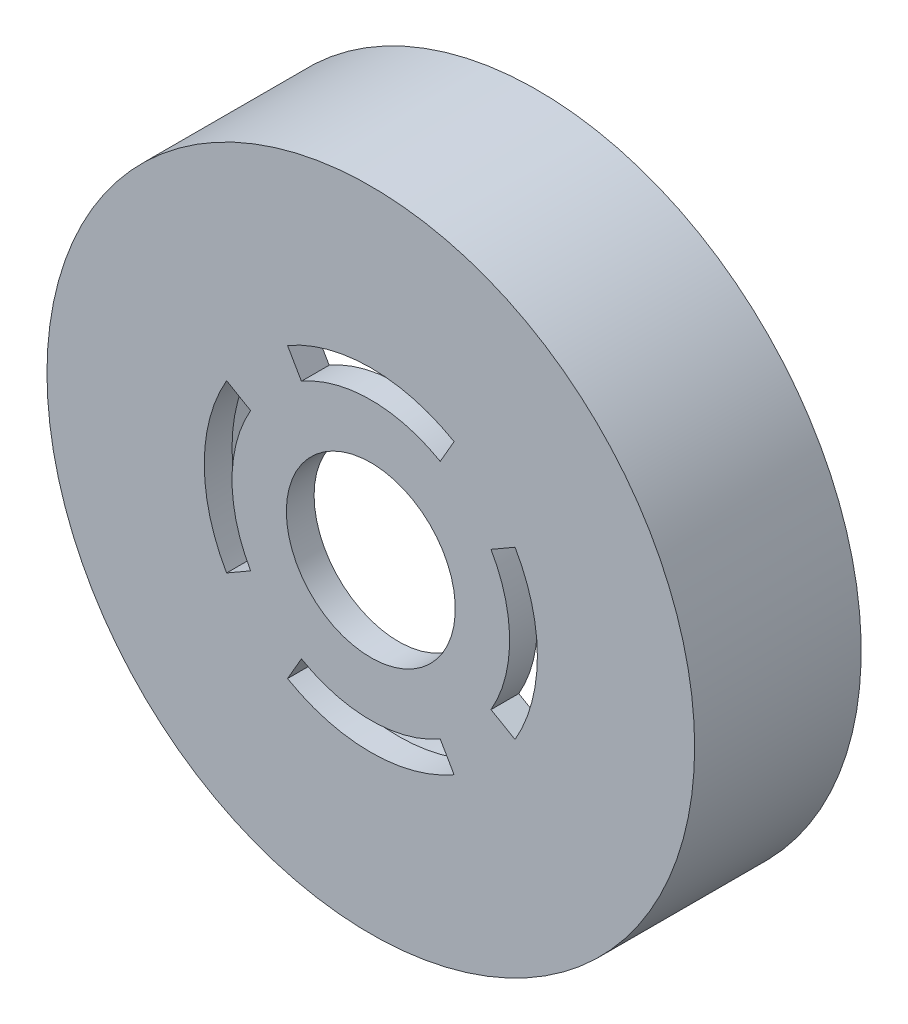
SolidWorks part; units mm, degrees
ref_plane "前视基准面" through (0, 0, 0) normal (0, 0, 1) x (1, 0, 0)
ref_plane "上视基准面" through (0, 0, 0) normal (0, 1, 0) x (1, 0, 0)
ref_plane "右视基准面" through (0, 0, 0) normal (1, 0, 0) x (0, 0, -1)
other "Configuration Table"
sketch "草图2" plane through (0, 0, 0) normal (0, 0, 1) x (1, 0, 0)
  circle A0 centre (0, 0) radius 35
  circle A1 centre (0, 0) radius 5.5
  dimension "D1" = 70
  dimension "D2" = 11
extrude "凸台-拉伸1" add sketch "草图2" along normal blind 5
sketch "草图3" plane through (0, 0, 0) normal (0, 0, -1) x (-1, 0, 0)
  circle A0 centre (0, 0) radius 30.1
  circle A1 centre (0, 0) radius 35
  dimension "D1" = 60.2
extrude "凸台-拉伸2" add sketch "草图3" along normal blind 15
sketch "草图4" plane through (0, 0, -15) normal (0, 0, -1) x (-1, 0, 0)
  line L0 (0, 0) -> (0, 32.5)
  line L1 (0, 0) -> (32.5, 0)
  line L2 (0, 0) -> (0, -32.5)
  line L3 (0, 0) -> (-32.5, 0)
  circle A0 centre (0, 32.5) radius 1.55
  circle A1 centre (32.5, 0) radius 1.55
  circle A2 centre (0, -32.5) radius 1.55
  circle A3 centre (-32.5, 0) radius 1.55
  point P9 (0, 0)
  point P17 (0, 0)
  dimension "D2" = 4
  dimension "D1" = 4
extrude "切除-拉伸1" cut sketch "草图4" against normal blind 10 contours A0 | A1 | A2 | A3 region at (1.065, 33.565, -15) region at (-32.5, 1.5062, -15) region at (-1.065, -31.435, -15) region at (34.0062, 0, -15)
sketch "草图9" plane through (0, 0, -15) normal (0, 0, -1) x (-1, 0, 0)
  line L0 (0, 0) -> (0, 32.5) construction
  line L1 (0, 0) -> (-21.2839, 21.2839) construction
  circle A0 centre (0, 0) radius 30.1 construction
  arc A1 (-22.0133, 20.5286) -> (-20.5286, 22.0133) centre (-21.2839, 21.2839) cw
  arc A2 (20.5286, 22.0133) -> (22.0133, 20.5286) centre (21.2839, 21.2839) cw
  arc A3 (22.0133, -20.5286) -> (20.5286, -22.0133) centre (21.2839, -21.2839) cw
  arc A4 (-20.5286, -22.0133) -> (-22.0133, -20.5286) centre (-21.2839, -21.2839) cw
  arc A5 (-20.5286, 22.0133) -> (-22.0133, 20.5286) centre (0, 0) ccw
  arc A6 (-22.0133, -20.5286) -> (-20.5286, -22.0133) centre (0, 0) ccw
  arc A7 (20.5286, -22.0133) -> (22.0133, -20.5286) centre (0, 0) ccw
  arc A8 (22.0133, 20.5286) -> (20.5286, 22.0133) centre (0, 0) ccw
  point P21 (0, 0)
  dimension "D2" = 1.05
  dimension "D1" = 45
  dimension "D3" = 4
extrude "切除-拉伸5" cut sketch "草图9" against normal up to surface (15 mm away) up to face at (5.5, 0, 0)
fillet "圆角1" radius 1 4 edges at (0, -30.1, -15) (-30.1, 0, -15) (0, 30.1, -15) (30.1, 0, -15)
sketch "草图10" plane through (0, 0, 5) normal (0, 0, 1) x (1, 0, 0)
  circle A0 centre (0, 0) radius 35
extrude "切除-拉伸6" cut sketch "草图10" against normal blind 2
sketch "草图11" plane through (0, 0, 0) normal (0, 0, -1) x (-1, 0, 0)
  line L0 (0, 0) -> (0, 32.5) construction
  line L1 (0, 0) -> (32.5, 0) construction
  line L2 (12.9904, 7.5) -> (15.5885, 9)
  line L3 (-7.5, 12.9904) -> (-9, 15.5885)
  line L4 (7.5, 12.9904) -> (9, 15.5885)
  line L5 (12.9904, -7.5) -> (15.5885, -9)
  line L6 (0, 0) -> (0, -32.5) construction
  line L7 (7.5, -12.9904) -> (9, -15.5885)
  line L8 (-7.5, -12.9904) -> (-9, -15.5885)
  line L9 (0, 0) -> (-32.5, 0) construction
  line L10 (-12.9904, -7.5) -> (-15.5885, -9)
  line L11 (-12.9904, 7.5) -> (-15.5885, 9)
  arc A1 (7.5, 12.9904) -> (-7.5, 12.9904) centre (0, 0) ccw
  arc A2 (9, 15.5885) -> (-9, 15.5885) centre (0, 0) ccw
  arc A3 (12.9904, -7.5) -> (12.9904, 7.5) centre (0, 0) ccw
  arc A4 (15.5885, -9) -> (15.5885, 9) centre (0, 0) ccw
  arc A5 (-7.5, -12.9904) -> (7.5, -12.9904) centre (0, 0) ccw
  arc A6 (-9, -15.5885) -> (9, -15.5885) centre (0, 0) ccw
  arc A7 (-12.9904, 7.5) -> (-12.9904, -7.5) centre (0, 0) ccw
  arc A8 (-15.5885, 9) -> (-15.5885, -9) centre (0, 0) ccw
  point P26 (0, 0)
  dimension "D4" = 30
  dimension "D1" = 4
extrude "切除-拉伸7" cut sketch "草图11" against normal blind 10
sketch "Sketch1" plane through (0, 0, 0) normal (0, 0, -1) x (-1, 0, 0)
  circle A0 centre (0, 0) radius 9.1308
extrude "Cut-Extrude1" cut sketch "Sketch1" against normal through all
